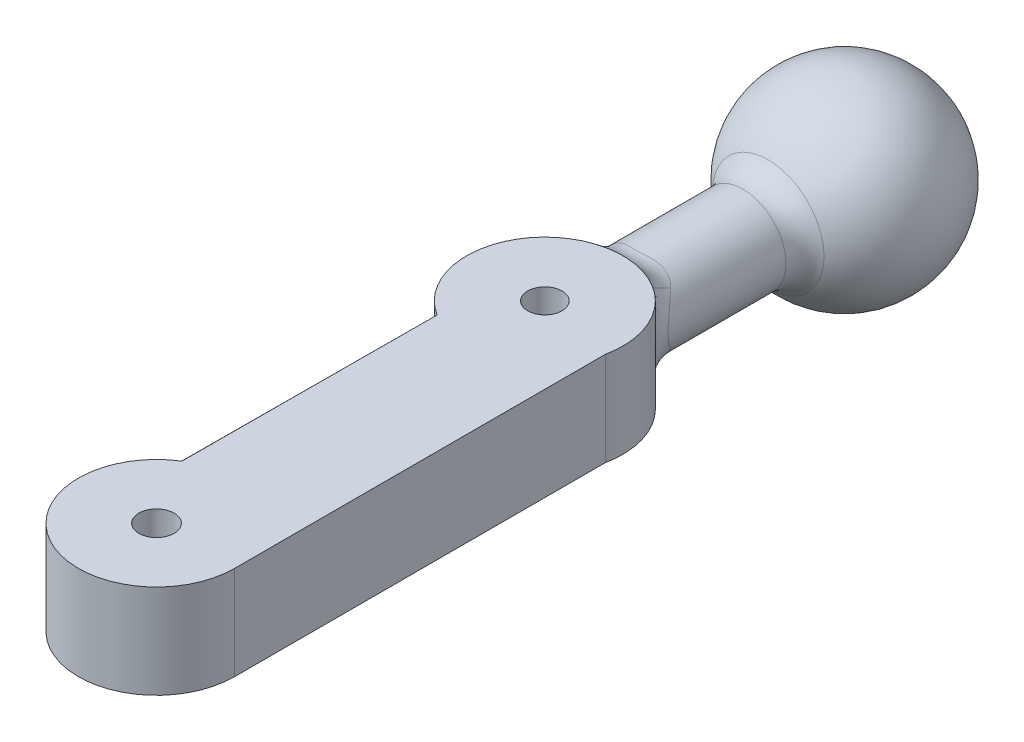
SolidWorks part; units mm, degrees
material "高韧性光敏树脂"
ref_plane "前视基准面" through (0, 0, 0) normal (0, 0, 1) x (1, 0, 0)
ref_plane "上视基准面" through (0, 0, 0) normal (0, 1, 0) x (1, 0, 0)
ref_plane "右视基准面" through (0, 0, 0) normal (1, 0, 0) x (0, 0, -1)
sketch "草图1" plane through (0, 0, 0) normal (0, 0, 1) x (1, 0, 0)
  line L0 (0, 2.42) -> (0, -2.42)
  circle A0 centre (0, 0) radius 2.42
  dimension "D1" = 4.84
revolve "旋转1" add sketch "草图1" angle 360 about L0 region at (-1.0271, 0, 0)
sketch "草图2" plane through (0, 0, 0) normal (0, 0, 1) x (1, 0, 0)
  circle A0 centre (0, 0) radius 1.1
  dimension "D1" = 2.2
extrude "凸台-拉伸1" add sketch "草图2" along normal blind 17.6064
sketch "草图3" plane through (0, 0, 0) normal (0, 1, 0) x (1, 0, 0)
  line L0 (-1.1, -17.6064) -> (1.1, -17.6064) construction
  circle A0 centre (0, -17.6064) radius 2
  circle A1 centre (0, -17.6064) radius 0.45
  dimension "D1" = 0.9
  dimension "D2" = 4
extrude "切除-拉伸1" cut sketch "草图3" against normal through all both and the other way through all contours A0
extrude "凸台-拉伸2" add sketch "草图3<3>" along normal mid plane 2.4
sketch "草图3<3>" plane through (0, 0, 0) normal (0, 1, 0) x (1, 0, 0) same geometry as "草图3"
ref_axis "基准轴1" through (0, 0, 16.0148) along (0, 0, -1)
ref_plane "基准面1" through (0, 0, 14) normal (0, 0, 1) x (1, 0, 0)
sketch "草图7" plane through (0, 1.2, 0) normal (0, 1, 0) x (1, 0, 0)
  line L1 (0, -17.6064) -> (0.0415, -7.7106) construction
  line L2 (0, -16.0148) -> (0, -2.1556) construction
  line L3 (0, -17.6064) -> (2, -17.6148) construction
  line L4 (2, -17.6148) -> (2.0414, -7.719) construction
  line L5 (2.0414, -7.719) -> (0.0415, -7.7106) construction
  line L6 (0.0415, -7.7106) -> (-1.9585, -7.7022) construction
  line L7 (-1.9585, -7.7022) -> (-2, -17.598) construction
  line L8 (0, -17.6064) -> (-2, -17.598) construction
  circle A0 centre (0, -17.6064) radius 0.45 construction
  circle A1 centre (0, -17.6064) radius 0.45
  circle A2 centre (0.0415, -7.7106) radius 0.44
  circle A3 centre (0.0415, -7.7106) radius 2
  circle A4 centre (0, -17.6064) radius 2 construction
  circle A6 centre (0, -17.6064) radius 2
  circle A8 centre (0, -17.6064) radius 2
  point P19 (0.0207, -12.6585)
  dimension "D1" = 0.88
  dimension "D4" = 4
  dimension "D5" = 0.24
  dimension "D2" = 9.8959
  dimension "D3" = 0
extrude "凸台-拉伸8" add sketch "草图7" against normal up to surface (2.4 mm away) contours A3 A2 region at (-1.902, 1.2, 7.7106) up to face at (0, -1.2, 19.6064)
ref_plane "基准面2" through (0, 0, 5) normal (0, 0, 1) x (1, 0, 0)
sketch "草图9" plane through (0, 0, 5) normal (0, 0, 1) x (1, 0, 0)
  circle A0 centre (0, 0) radius 0.75
  dimension "D1" = 1.5
ref_plane "基准面3" through (0.0207, 1.2, 12.6585) normal (0.0042, 0, -1) x (-1, 0, -0.0042)
sketch "草图10" plane through (0.0207, 1.2, 12.6585) normal (0.0042, 0, -1) x (-1, 0, -0.0042)
  line L0 (0, 0) -> (0, -2.4) construction
  line L2 (-2, -2.4) -> (2, -2.4) construction
  line L3 (-2, -2.4) -> (2, -2.4)
  line L4 (2, 0) -> (-2, 0) construction
  line L5 (2, 0) -> (-2, 0)
  line L6 (-2, 0) -> (-2, -2.4)
  line L7 (2, 0) -> (2, -2.4)
  circle A0 centre (0, -1.2) radius 1.6
  dimension "D1" = 3.2
extrude "凸台-拉伸9" add sketch "草图10" along normal up to surface and the other way up to surface contours L0 L5 A0 L3 | L5 L0 L3 A0 region at (-0.7046, 0, 12.6555) region at (0.7461, 0, 12.6615) up to face at (0.0415, -1.2, 9.7106) other way up to face at (0, -1.2, 19.6064)
ref_axis "基准轴2" through (0.0415, -1.2, 7.7106) along (0, 1, 0)
ref_axis "基准轴3" through (0.0415, -1.2, 7.7106) along (0, 1, 0)
sketch "草图11" plane through (0, 1.2, 0) normal (0, 1, 0) x (1, 0, 0)
  circle A0 centre (0.0415, -7.7106) radius 0.44 construction
  circle A1 centre (0.0415, -7.7106) radius 0.44
extrude "切除-拉伸2" cut sketch "草图11" against normal through all
ref_plane "基准面4" through (0, 0, 10) normal (0, 0, 1) x (1, 0, 0)
sketch "草图12" plane through (0, 0, 10) normal (0, 0, 1) x (1, 0, 0)
  line L0 (0, 0) -> (0, 1.2)
  line L1 (2, 1.2) -> (-2, 1.2) construction
  line L2 (0, 1.2) -> (2, 1.2)
  line L3 (2, 1.2) -> (2, -1.2)
  line L4 (0, 0) -> (0, -1.2)
  line L7 (-2, -1.2) -> (2, -1.2) construction
  line L8 (0, -1.2) -> (2, -1.2)
  dimension "D1" = 2
extrude "凸台-拉伸10" add sketch "草图12" against normal up to body and the other way up to body
fillet "圆角1" radius 0.8 2 edges at (1.0965, -0.0882, 6.0115) (-1.1, 0, 2.1556)
equation "\"d\"= 10"
equation "\"l\"= 13.52"
equation "\"L1\"= 8.283"
equation "\"th\"= 52.956771"
equation "\"k\"= 0.8"
equation "\"D1@凸台-拉伸1\"=\"l\"*\"k\""
equation "\"0。42\"=0.84"
equation "\"0。4\"=10"
